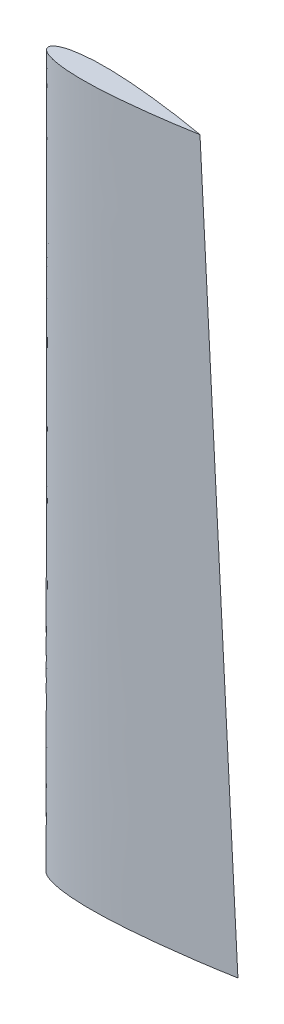
SolidWorks part; units mm, degrees
ref_plane "Front Plane" through (0, 0, 0) normal (0, 0, 1) x (1, 0, 0)
ref_plane "Top Plane" through (0, 0, 0) normal (0, 1, 0) x (1, 0, 0)
ref_plane "Right Plane" through (0, 0, 0) normal (1, 0, 0) x (0, 0, -1)
sketch "rootSketch" plane through (0, 0, 0) normal (0, 1, 0) x (1, 0, 0)
  line L0 (0, 0) -> (1500, 0) construction
  line L2 (130, -39) -> (130, 39) construction
  line L3 (0, 0) -> (520, 0) construction
  spline S0 degree 4 poles (0, 0) (-0.0001, 0.5654) (0.0536, 1.4802) (0.2607, 2.8027) (0.7777, 4.522) (1.4706, 6.1188) (2.4853, 7.8597) (3.9236, 9.7755) (5.9919, 11.9542) (9.0582, 14.5182) (13.7048, 17.5792) (20.7825, 21.1911) (31.7576, 25.4204) (48.232, 29.987) (72.7551, 34.5297) (104.3849, 37.8048) (136.2818, 39.0905) (166.3809, 39.0862) (196.4662, 38.3106) (221.5182, 37.1099) (246.5436, 35.4647) (271.5411, 33.4472) (291.522, 31.6348) (311.4856, 29.6435) (331.4329, 27.4893) (348.8708, 25.4726) (363.8089, 23.6551) (376.2472, 22.0838) (386.1986, 20.7921) (398.6215, 19.1378) (413.5397, 17.0827) (430.8967, 14.595) (450.7686, 11.6077) (468.0611, 8.8865) (482.9855, 6.442) (495.2251, 4.3757) (504.1169, 2.835) (511.0796, 1.6079) (518.469, 0.2799) (522.2276, -0.4041) (527.6198, -1.3949) (532.051, -2.2221) (537.2004, -3.1898) (542.7114, -4.2436) (549.3261, -5.5266) (555.7484, -6.7962) (561.4804, -7.9471) (565.909, -8.8508) (569.1689, -9.5219) (570.7832, -9.8566) (571.594, -10.0251) (571.9999, -10.1096) knots 0 0 0 0 0 0.003841 0.006235 0.009072 0.012193 0.015657 0.019917 0.025339 0.032593 0.042799 0.057705 0.079311 0.112503 0.158973 0.227236 0.2955 0.329632 0.363764 0.432028 0.46616 0.500292 0.534424 0.568556 0.602688 0.63682 0.653886 0.670952 0.688018 0.705084 0.739215 0.773347 0.807479 0.841611 0.858677 0.875743 0.892809 0.901342 0.909875 0.921141 0.926774 0.932406 0.943672 0.954938 0.966203 0.977469 0.988734 0.994367 0.997184 1 1 1 1 1 construction
  spline S1 degree 4 poles (0, 0) (-0.0001, 0.5654) (0.0536, 1.4802) (0.2607, 2.8027) (0.7777, 4.522) (1.4706, 6.1188) (2.4853, 7.8597) (3.9236, 9.7755) (5.9919, 11.9542) (9.0582, 14.5182) (13.7048, 17.5792) (20.7825, 21.1911) (31.7576, 25.4204) (48.232, 29.987) (72.7551, 34.5297) (104.3849, 37.8048) (136.2818, 39.0905) (166.3809, 39.0862) (196.4662, 38.3106) (221.5182, 37.1099) (246.5436, 35.4647) (271.5411, 33.4472) (291.522, 31.6348) (311.4856, 29.6435) (331.4329, 27.4893) (348.8708, 25.4726) (363.8089, 23.6551) (376.2472, 22.0838) (386.1986, 20.7921) (398.6215, 19.1378) (413.5397, 17.0827) (430.8967, 14.595) (450.7686, 11.6077) (468.0611, 8.8865) (482.9855, 6.442) (495.2251, 4.3757) (504.1169, 2.835) (511.0796, 1.6079) (516.6353, 0.6095) (518.8775, 0.2039) (520, 0) knots 0 0 0 0 0 0.003841 0.006235 0.009072 0.012193 0.015657 0.019917 0.025339 0.032593 0.042799 0.057705 0.079311 0.112503 0.158973 0.227236 0.2955 0.329632 0.363764 0.432028 0.46616 0.500292 0.534424 0.568556 0.602688 0.63682 0.653886 0.670952 0.688018 0.705084 0.739215 0.773347 0.807479 0.841611 0.858677 0.875743 0.892809 0.901342 0.909875 0.909875 0.909875 0.909875 0.909875
  spline S2 degree 4 poles (0, 0) (-0.0001, -0.5654) (0.0536, -1.4802) (0.2607, -2.8027) (0.7777, -4.522) (1.4706, -6.1188) (2.4853, -7.8597) (3.9236, -9.7755) (5.9919, -11.9542) (9.0582, -14.5182) (13.7048, -17.5792) (20.7825, -21.1911) (31.7576, -25.4204) (48.232, -29.987) (72.7551, -34.5297) (104.3849, -37.8048) (136.2818, -39.0905) (166.3809, -39.0862) (196.4662, -38.3106) (221.5182, -37.1099) (246.5436, -35.4647) (271.5411, -33.4472) (291.522, -31.6348) (311.4856, -29.6435) (331.4329, -27.4893) (348.8708, -25.4726) (363.8089, -23.6551) (376.2472, -22.0838) (386.1986, -20.7921) (398.6215, -19.1378) (413.5397, -17.0827) (430.8967, -14.595) (450.7686, -11.6077) (468.0611, -8.8865) (482.9855, -6.442) (495.2251, -4.3757) (504.1169, -2.835) (511.0796, -1.6079) (518.469, -0.2799) (522.2276, 0.4041) (527.6198, 1.3949) (532.051, 2.2221) (537.2004, 3.1898) (542.7114, 4.2436) (549.3261, 5.5266) (555.7484, 6.7962) (561.4804, 7.9471) (565.909, 8.8508) (569.1689, 9.5219) (570.7832, 9.8566) (571.594, 10.0251) (571.9999, 10.1096) knots 0 0 0 0 0 0.003841 0.006235 0.009072 0.012193 0.015657 0.019917 0.025339 0.032593 0.042799 0.057705 0.079311 0.112503 0.158973 0.227236 0.2955 0.329632 0.363764 0.432028 0.46616 0.500292 0.534424 0.568556 0.602688 0.63682 0.653886 0.670952 0.688018 0.705084 0.739215 0.773347 0.807479 0.841611 0.858677 0.875743 0.892809 0.901342 0.909875 0.921141 0.926774 0.932406 0.943672 0.954938 0.966203 0.977469 0.988734 0.994367 0.997184 1 1 1 1 1 construction
  spline S3 degree 4 poles (0, 0) (-0.0001, -0.5654) (0.0536, -1.4802) (0.2607, -2.8027) (0.7777, -4.522) (1.4706, -6.1188) (2.4853, -7.8597) (3.9236, -9.7755) (5.9919, -11.9542) (9.0582, -14.5182) (13.7048, -17.5792) (20.7825, -21.1911) (31.7576, -25.4204) (48.232, -29.987) (72.7551, -34.5297) (104.3849, -37.8048) (136.2818, -39.0905) (166.3809, -39.0862) (196.4662, -38.3106) (221.5182, -37.1099) (246.5436, -35.4647) (271.5411, -33.4472) (291.522, -31.6348) (311.4856, -29.6435) (331.4329, -27.4893) (348.8708, -25.4726) (363.8089, -23.6551) (376.2472, -22.0838) (386.1986, -20.7921) (398.6215, -19.1378) (413.5397, -17.0827) (430.8967, -14.595) (450.7686, -11.6077) (468.0611, -8.8865) (482.9855, -6.442) (495.2251, -4.3757) (504.1169, -2.835) (511.0796, -1.6079) (516.6353, -0.6095) (518.8775, -0.2039) (520, 0) knots 0 0 0 0 0 0.003841 0.006235 0.009072 0.012193 0.015657 0.019917 0.025339 0.032593 0.042799 0.057705 0.079311 0.112503 0.158973 0.227236 0.2955 0.329632 0.363764 0.432028 0.46616 0.500292 0.534424 0.568556 0.602688 0.63682 0.653886 0.670952 0.688018 0.705084 0.739215 0.773347 0.807479 0.841611 0.858677 0.875743 0.892809 0.901342 0.909875 0.909875 0.909875 0.909875 0.909875
  point P10 (130, 0)
  dimension "incidenceAngle" = 0
  dimension "rootChord" = 520
  dimension "rootQuarterChord" = 130
  dimension "rootMaxThickness" = 78
ref_plane "Plane1" through (0, 1950.0156, 0) normal (0, 1, 0) x (1, 0, 0)
sketch "tipSketch" plane through (0, 1950.0156, 0) normal (0, 1, 0) x (1, 0, 0)
  line L0 (216.8234, 0) -> (518.1352, 0) construction
  line L3 (0, 0) -> (416, 0) construction
  line L4 (104, -31.2) -> (104, 31.2) construction
  spline S0 degree 4 poles (0, 0) (-0.0001, 0.4526) (0.0429, 1.1842) (0.2086, 2.2419) (0.6222, 3.6177) (1.1765, 4.895) (1.9882, 6.2878) (3.1389, 7.8203) (4.7935, 9.5634) (7.2466, 11.6145) (10.9638, 14.0633) (16.626, 16.9529) (25.4061, 20.3363) (38.5856, 23.9896) (58.2041, 27.6238) (83.5079, 30.2438) (109.0255, 31.2724) (133.1047, 31.269) (157.1729, 30.6485) (177.2146, 29.6879) (197.2349, 28.3717) (217.2329, 26.7577) (233.2176, 25.3079) (249.1886, 23.7148) (265.1461, 21.9915) (279.097, 20.378) (291.0466, 18.9242) (300.9987, 17.6669) (308.9572, 16.634) (318.9003, 15.3097) (330.8261, 13.6672) (344.7266, 11.6743) (360.6007, 9.2888) (374.4705, 7.1053) (386.3552, 5.1597) (395.2488, 3.6571) (400.7019, 2.7171) (404.6252, 2.0315) (407.6573, 1.4968) (410.4147, 1.0078) (414.7874, 0.2217) (418.3137, -0.42) (424.2238, -1.5084) (428.7757, -2.367) (434.3776, -3.4328) (439.3296, -4.3974) (444.6898, -5.4535) (449.7621, -6.4751) (453.7451, -7.2876) (456.2875, -7.8149) (457.6029, -8.0882) knots 0 0 0 0 0 0.003841 0.006235 0.009072 0.012193 0.015657 0.019917 0.025339 0.032593 0.042799 0.057705 0.079311 0.112503 0.158973 0.227236 0.2955 0.329632 0.363764 0.432028 0.46616 0.500292 0.534424 0.568556 0.602688 0.63682 0.653886 0.670952 0.688018 0.705084 0.739215 0.773347 0.807479 0.841611 0.858677 0.875743 0.884276 0.888543 0.892809 0.901342 0.909875 0.921141 0.932406 0.943672 0.954938 0.966203 0.977469 0.988734 1 1 1 1 1 construction
  spline S1 degree 4 poles (0, 0) (-0.0001, 0.4526) (0.0429, 1.1842) (0.2086, 2.2419) (0.6222, 3.6177) (1.1765, 4.895) (1.9882, 6.2878) (3.1389, 7.8203) (4.7935, 9.5634) (7.2466, 11.6145) (10.9638, 14.0633) (16.626, 16.9529) (25.4061, 20.3363) (38.5856, 23.9896) (58.2041, 27.6238) (83.5079, 30.2438) (109.0255, 31.2724) (133.1047, 31.269) (157.1729, 30.6485) (177.2146, 29.6879) (197.2349, 28.3717) (217.2329, 26.7577) (233.2176, 25.3079) (249.1886, 23.7148) (265.1461, 21.9915) (279.097, 20.378) (291.0466, 18.9242) (300.9987, 17.6669) (308.9572, 16.634) (318.9003, 15.3097) (330.8261, 13.6672) (344.7266, 11.6743) (360.6007, 9.2888) (374.4705, 7.1053) (386.3552, 5.1597) (395.2488, 3.6571) (400.7019, 2.7171) (404.6252, 2.0315) (407.6573, 1.4968) (410.4147, 1.0078) (413.2762, 0.4934) (415.102, 0.1632) (416, 0) knots 0 0 0 0 0 0.003841 0.006235 0.009072 0.012193 0.015657 0.019917 0.025339 0.032593 0.042799 0.057705 0.079311 0.112503 0.158973 0.227236 0.2955 0.329632 0.363764 0.432028 0.46616 0.500292 0.534424 0.568556 0.602688 0.63682 0.653886 0.670952 0.688018 0.705084 0.739215 0.773347 0.807479 0.841611 0.858677 0.875743 0.884276 0.888543 0.892809 0.901342 0.909875 0.909875 0.909875 0.909875 0.909875
  spline S2 degree 4 poles (0, 0) (-0.0001, -0.4526) (0.0429, -1.1842) (0.2086, -2.2419) (0.6222, -3.6177) (1.1765, -4.895) (1.9882, -6.2878) (3.1389, -7.8203) (4.7935, -9.5634) (7.2466, -11.6145) (10.9638, -14.0633) (16.626, -16.9529) (25.4061, -20.3363) (38.5856, -23.9896) (58.2041, -27.6238) (83.5079, -30.2438) (109.0255, -31.2724) (133.1047, -31.269) (157.1729, -30.6485) (177.2146, -29.6879) (197.2349, -28.3717) (217.2329, -26.7577) (233.2176, -25.3079) (249.1886, -23.7148) (265.1461, -21.9915) (279.097, -20.378) (291.0466, -18.9242) (300.9987, -17.6669) (308.9572, -16.634) (318.9003, -15.3097) (330.8261, -13.6672) (344.7266, -11.6743) (360.6007, -9.2888) (374.4705, -7.1053) (386.3552, -5.1597) (395.2488, -3.6571) (400.7019, -2.7171) (404.6252, -2.0315) (407.6573, -1.4968) (410.4147, -1.0078) (414.7874, -0.2217) (418.3137, 0.42) (424.2238, 1.5084) (428.7757, 2.367) (434.3776, 3.4328) (439.3296, 4.3974) (444.6898, 5.4535) (449.7621, 6.4751) (453.7451, 7.2876) (456.2875, 7.8149) (457.6029, 8.0882) knots 0 0 0 0 0 0.003841 0.006235 0.009072 0.012193 0.015657 0.019917 0.025339 0.032593 0.042799 0.057705 0.079311 0.112503 0.158973 0.227236 0.2955 0.329632 0.363764 0.432028 0.46616 0.500292 0.534424 0.568556 0.602688 0.63682 0.653886 0.670952 0.688018 0.705084 0.739215 0.773347 0.807479 0.841611 0.858677 0.875743 0.884276 0.888543 0.892809 0.901342 0.909875 0.921141 0.932406 0.943672 0.954938 0.966203 0.977469 0.988734 1 1 1 1 1 construction
  spline S3 degree 4 poles (0, 0) (-0.0001, -0.4526) (0.0429, -1.1842) (0.2086, -2.2419) (0.6222, -3.6177) (1.1765, -4.895) (1.9882, -6.2878) (3.1389, -7.8203) (4.7935, -9.5634) (7.2466, -11.6145) (10.9638, -14.0633) (16.626, -16.9529) (25.4061, -20.3363) (38.5856, -23.9896) (58.2041, -27.6238) (83.5079, -30.2438) (109.0255, -31.2724) (133.1047, -31.269) (157.1729, -30.6485) (177.2146, -29.6879) (197.2349, -28.3717) (217.2329, -26.7577) (233.2176, -25.3079) (249.1886, -23.7148) (265.1461, -21.9915) (279.097, -20.378) (291.0466, -18.9242) (300.9987, -17.6669) (308.9572, -16.634) (318.9003, -15.3097) (330.8261, -13.6672) (344.7266, -11.6743) (360.6007, -9.2888) (374.4705, -7.1053) (386.3552, -5.1597) (395.2488, -3.6571) (400.7019, -2.7171) (404.6252, -2.0315) (407.6573, -1.4968) (410.4147, -1.0078) (413.2762, -0.4934) (415.102, -0.1632) (416, 0) knots 0 0 0 0 0 0.003841 0.006235 0.009072 0.012193 0.015657 0.019917 0.025339 0.032593 0.042799 0.057705 0.079311 0.112503 0.158973 0.227236 0.2955 0.329632 0.363764 0.432028 0.46616 0.500292 0.534424 0.568556 0.602688 0.63682 0.653886 0.670952 0.688018 0.705084 0.739215 0.773347 0.807479 0.841611 0.858677 0.875743 0.884276 0.888543 0.892809 0.901342 0.909875 0.909875 0.909875 0.909875 0.909875
  point P10 (104, 0)
  dimension "incidenceAngle" = 0
  dimension "tipChord" = 416
  dimension "tipQuarterChord" = 104
  dimension "tipMaxThickness" = 62.4
  dimension "sweepOffset" = 0
  dimension "D1" = 0
  dimension "D2" = 0
loft "Loft1" add profiles "rootSketch", "tipSketch" connector at (0, 0, 0) connector at (0, 1950.0156, 0)
ref_plane "Plane2" through (520, 0, 0) normal (1, 0, 0) x (0, 0, -1)
sketch "rudderSketch" plane through (0, 0, 0) normal (0, 0, 1) x (1, 0, 0)
  line L0 (0, 0) -> (0, 487.5039) construction
  line L1 (0, 0) -> (0, 1462.5117) construction
  line L2 (0, 487.5039) -> (247, 487.5039) construction
  line L3 (0, 1462.5117) -> (247, 1462.5117) construction
  line L4 (247, 1462.5117) -> (247, 487.5039)
  line L5 (247, 1462.5117) -> (767, 1462.5117)
  line L6 (247, 487.5039) -> (767, 487.5039)
  line L7 (767, 487.5039) -> (767, 1462.5117)
  line L8 (763.1, 491.4039) -> (763.1, 1458.6117)
  line L9 (250.9, 1458.6117) -> (763.1, 1458.6117)
  line L10 (250.9, 1458.6117) -> (250.9, 491.4039)
  line L11 (250.9, 491.4039) -> (763.1, 491.4039)
  dimension "rudderStartyLoc" = 487.5039
  dimension "rudderEndyLoc" = 1462.5117
  dimension "rudderStartxLoc" = 247
  dimension "rudderEndeLoc" = 247
  dimension "D1" = 520
  dimension "D2" = 520
  dimension "D3" = 3.9
extrude "Cut-Extrude1" [suppressed] cut sketch "rudderSketch" against normal blind 200 and the other way blind 200
equation "\"rootChord\"= 0.52"
equation "\"NACAairfoil\"= 0015"
equation "\"incidentAngle\"= 0"
equation "\"aspectRatio\"= 4.1667"
equation "\"taperRatio\"= 0.8"
equation "\"sweepAngle\"= 0'V-stab sweep angle"
equation "\"rootChord@rootSketch\"=(\"rootChord\"+\"rootChord\")/2"
equation "\"incidenceAngle@rootSketch\"=(\"incidentAngle\"+\"incidentAngle\")/2"
equation "\"rootQuarterChord@rootSketch\" = \"rootChord@rootSketch\" / 4"
equation "\"rootMaxThickness@rootSketch\" = \"rootChord\" * \"NACAairfoil\" / 100"
equation "\"halfSpan@Plane1\"= \"rootChord@rootSketch\" * ( 1 + \"taperRatio\" ) / 2 * \"aspectRatio\""
equation "\"incidenceAngle@tipSketch\" = \"incidenceAngle@rootSketch\""
equation "\"tipChord@tipSketch\"= \"rootChord@rootSketch\" * \"taperRatio\""
equation "\"tipQuarterChord@tipSketch\"=\"tipChord@tipSketch\"/4"
equation "\"tipMaxThickness@tipSketch\"=\"tipChord@tipSketch\"*\"NACAairfoil\"/100"
equation "\"rootChord@Plane2\"=\"rootChord@rootSketch\""
equation "\"rudderCenter\"= 0.5'Center of the rudder as a percentage of half span"
equation "\"rudderWidth\"= 0.5'Width of the rudder as a percentage of half span"
equation "\"rudderStartyLoc@rudderSketch\"=\"halfSpan@Plane1\" *  ( \"rudderCenter\" - \"rudderWidth\" / 2 )"
equation "\"rudderEndyLoc@rudderSketch\"=\"halfSpan@Plane1\" *  ( \"rudderCenter\" + \"rudderWidth\" / 2 )"
equation "\"rudderStartxLoc@rudderSketch\"=\"rudderStartyLoc@rudderSketch\"*tan ( \"sweepAngle\" ) + 0.5*(\"rootChord@rootSketch\" + \"rudderStartyLoc@rudderSketch\"*(((\"tipChord@tipSketch\"-\"rootChord@rootSketch\")/\"halfSpan@Plane1\")))"
equation "\"rudderEndeLoc@rudderSketch\"=\"rudderStartyLoc@rudderSketch\"*tan ( \"sweepAngle\" ) + 0.5*(\"rootChord@rootSketch\" + \"rudderStartyLoc@rudderSketch\"*(((\"tipChord@tipSketch\"-\"rootChord@rootSketch\")/\"halfSpan@Plane1\")))"
equation "\"D1@rudderSketch\"=1*\"rootChord@rootSketch\""
equation "\"D2@rudderSketch\"=1*\"rootChord@rootSketch\""
equation "\"D3@rudderSketch\"=\"halfSpan@Plane1\"/500"
equation "\"sweepOffset@tipSketch\" = \"halfSpan@Plane1\" * tan ( \"sweepAngle\" ) "
equation "\"D2@tipSketch\"=\"tipChord@tipSketch\"*tan(\"incidentAngle\")"
